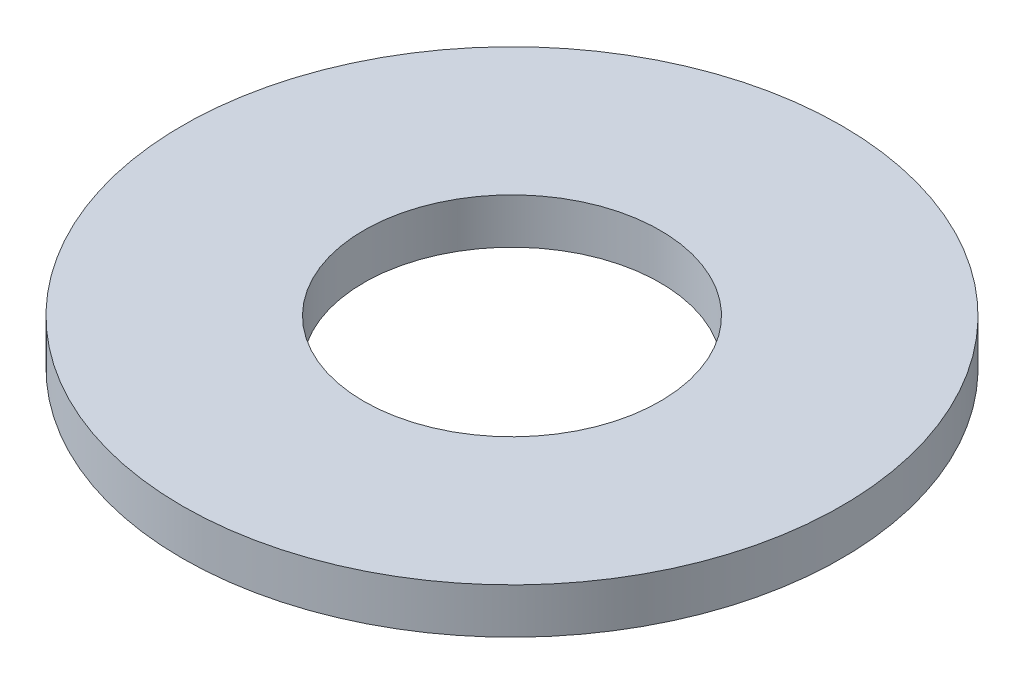
SolidWorks part; units mm, degrees
ref_plane "Front Plane" through (0, 0, 0) normal (0, 0, 1) x (1, 0, 0)
ref_plane "Top Plane" through (0, 0, 0) normal (0, 1, 0) x (1, 0, 0)
ref_plane "Right Plane" through (0, 0, 0) normal (1, 0, 0) x (0, 0, -1)
sketch "Sketch1" plane through (0, 0, 0) normal (0, 1, 0) x (1, 0, 0)
  circle A0 centre (0, 0) radius 7.9375
  dimension "OD" = 15.875
extrude "Boss-Extrude1" add sketch "Sketch1" along normal blind 1.0922
sketch "Sketch5" plane through (0, 1.0922, 0) normal (0, 1, 0) x (-1, 0, 0)
  circle A0 centre (0, 0) radius 3.5687
  dimension "ID" = 7.1374
extrude "Cut-Extrude1" cut sketch "Sketch5" against normal through all
ref_axis "Axis1" through (0, -0.0546, 0) along (0, 1, 0)
